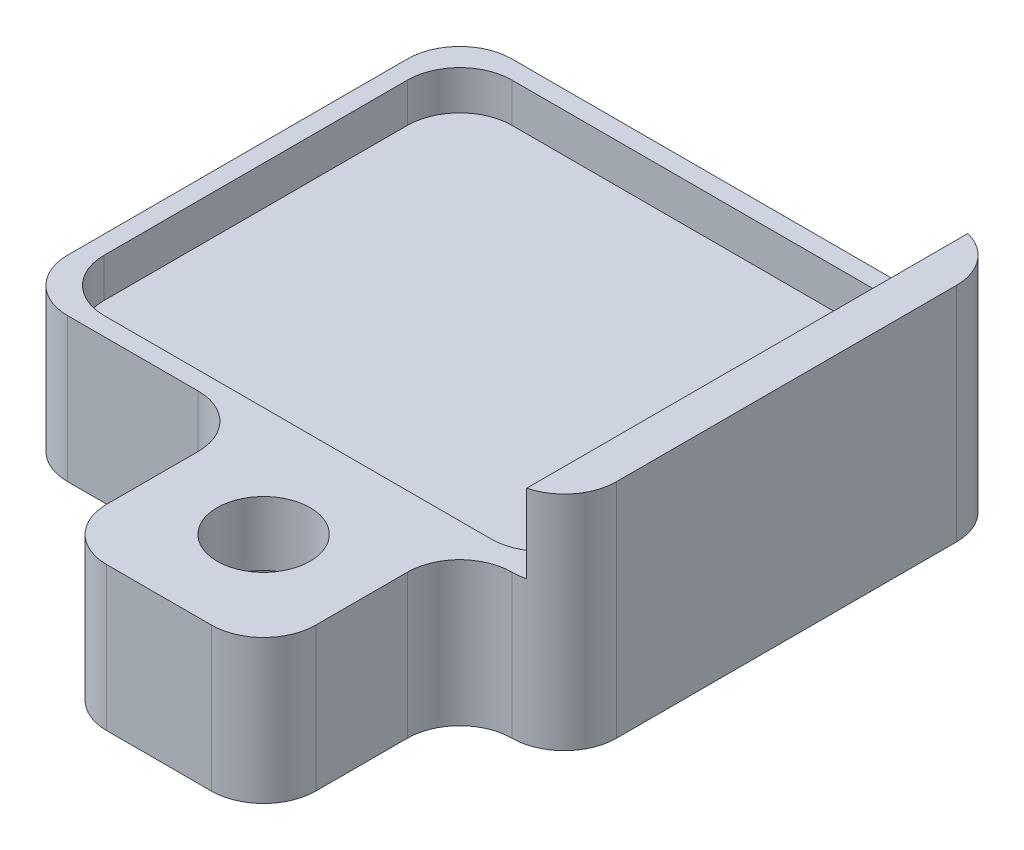
SolidWorks part; units mm, degrees
ref_plane "Front Plane" through (0, 0, 0) normal (0, 0, 1) x (1, 0, 0)
ref_plane "Top Plane" through (0, 0, 0) normal (0, 1, 0) x (1, 0, 0)
ref_plane "Right Plane" through (0, 0, 0) normal (1, 0, 0) x (0, 0, -1)
sketch "Sketch1" plane through (0, 0, 0) normal (0, 1, 0) x (1, 0, 0)
  line L1 (-5.25, -4.25) -> (5.25, -4.25)
  line L2 (-5.25, -4.25) -> (-5.25, 4.25)
  line L3 (-5.25, 4.25) -> (5.25, 4.25)
  line L4 (5.25, -4.25) -> (5.25, 4.25)
  line L5 (-5.25, -4.25) -> (5.25, 4.25) construction
  line L6 (-5.25, 4.25) -> (5.25, -4.25) construction
  point P0 (0, 0)
  dimension "D1" = 10.5
  dimension "D2" = 8.5
extrude "Extrude1" add sketch "Sketch1" along normal blind 4.25
sketch "Sketch3" plane through (0, 4.25, 0) normal (0, 1, 0) x (1, 0, 0)
  line L0 (-5.25, -4.25) -> (5.25, -4.25) construction
  line L1 (-5.25, 4.25) -> (4.5, 4.25)
  line L2 (-5.25, 4.25) -> (-5.25, -4.25)
  line L3 (-5.25, -4.25) -> (4.5, -4.25)
  line L4 (4.5, 4.25) -> (4.5, -4.25)
  dimension "D1" = 9.75
extrude "Extrude4" cut sketch "Sketch3" against normal blind 1.5
sketch "Sketch4" plane through (0, 2.75, 0) normal (0, 1, 0) x (1, 0, 0)
  line L0 (4.5, -4.25) -> (4.5, 4.25) construction
  line L1 (-4.9, -3.9) -> (4.5, -3.9)
  line L2 (-4.9, -3.9) -> (-4.9, 3.9)
  line L3 (-4.9, 3.9) -> (4.5, 3.9)
  line L4 (4.5, -3.9) -> (4.5, 3.9)
  line L5 (-4.9, -3.9) -> (4.5, 3.9) construction
  line L6 (-4.9, 3.9) -> (4.5, -3.9) construction
  line L7 (-5.25, 4.25) -> (-5.25, -4.25) construction
  line L8 (-5.25, -4.25) -> (4.5, -4.25) construction
  point P0 (-0.0128, -0.1553)
  dimension "D1" = 7.8
  dimension "D2" = 0.35
  dimension "D3" = 0.35
extrude "Extrude5" cut sketch "Sketch4" against normal blind 0.75
sketch "Sketch5" plane through (0, 0, 4.25) normal (0, 0, 1) x (1, 0, 0)
  line L0 (-5.25, 2.75) -> (4.5, 2.75) construction
  line L1 (-0.75, 2.75) -> (3.25, 2.75)
  line L2 (-0.75, 2.75) -> (-0.75, 0)
  line L3 (-0.75, 0) -> (3.25, 0)
  line L4 (3.25, 2.75) -> (3.25, 0)
  line L5 (-5.25, 0) -> (5.25, 0) construction
  line L6 (-5.25, 2.75) -> (-5.25, 0) construction
  dimension "D1" = 4.5
  dimension "D2" = 4
extrude "Extrude6" add sketch "Sketch5" along normal blind 3.75
hole_wizard "CBORE for #0 Socket Head Cap Screw1" positions "3DSketch1" profile "Sketch6" counterbore size "#0" standard "Ansi Inch" end condition through all
sketch3d "3DSketch1"
  line L0 (-0.75, 0, 8) -> (3.25, 0, 8) construction
  line L1 (-0.75, 0, 8) -> (-0.75, 0, 4.25) construction
  point P0 (1.25, 0, 6)
  dimension "D1" = 2
  dimension "D2" = 2
sketch "Sketch6" plane through (1.25, 0, 6) normal (1, 0, 0) x (0, 0, -1)
  line L0 (0, 0) -> (0, 4.25)
  line L1 (0, 4.25) -> (0.889, 4.25)
  line L3 (0.889, 4.25) -> (0.889, 1.524)
  line L4 (0.889, 1.524) -> (1.5875, 1.524)
  line L5 (1.5875, 1.524) -> (1.5875, 0)
  line L7 (1.5875, 0) -> (0, 0)
  line L11 (0, -6.35) -> (0, 107.95) construction
  dimension "Thru Hole Dia." = 1.778
  dimension "Thru Hole Depth" = 4.25
  dimension "C'Bore Dia." = 3.175
  dimension "C'Bore Depth" = 1.524
fillet "Fillet1" radius 1 12 edges at (5.25, 2.125, -4.25) (5.25, 2.125, 4.25) (3.25, 1.375, 8) (-0.75, 1.375, 8) (-5.25, 1.375, -4.25) (-5.25, 1.375, 4.25) (4.5, 2.375, -3.9) (-4.9, 2.375, -3.9) (-4.9, 2.375, 3.9) (4.5, 2.375, 3.9)
